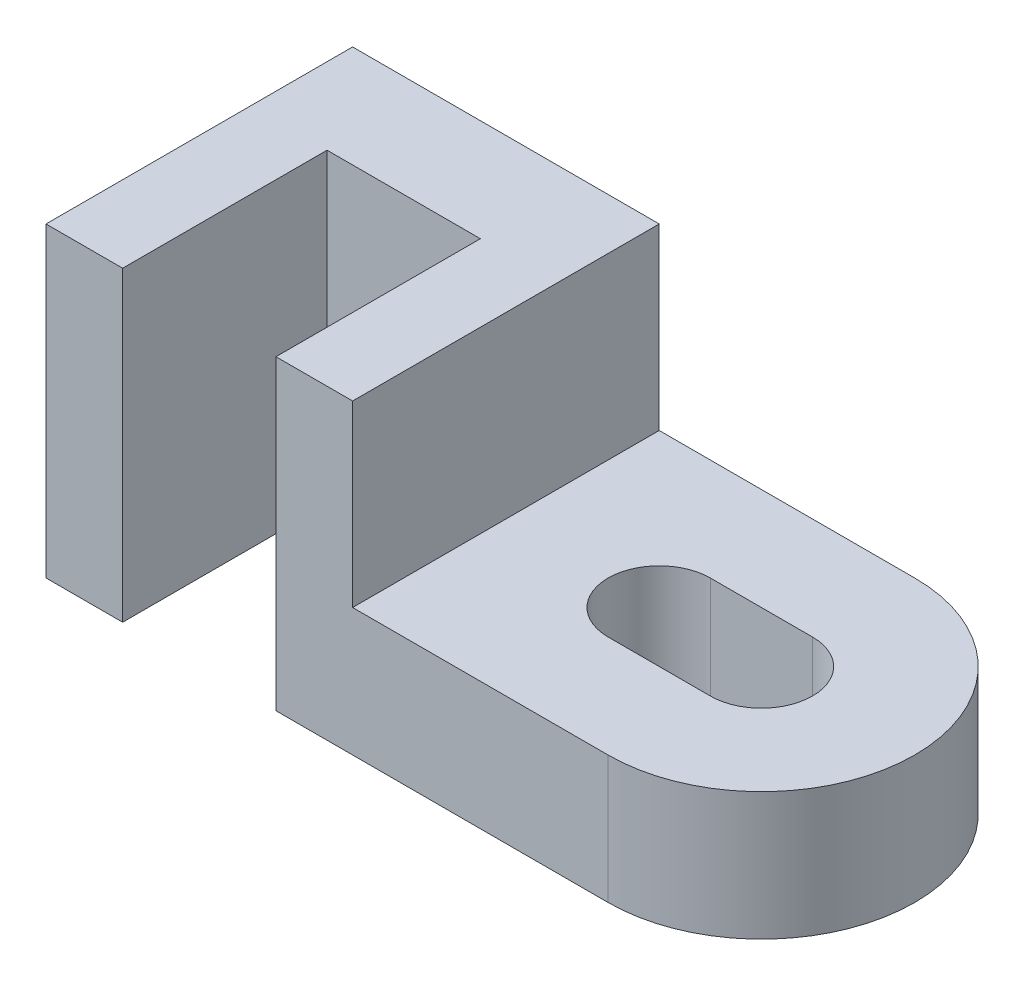
SolidWorks part; units mm, degrees
ref_plane "Front Plane" through (0, 0, 0) normal (0, 0, 1) x (1, 0, 0)
ref_plane "Top Plane" through (0, 0, 0) normal (0, 1, 0) x (1, 0, 0)
ref_plane "Right Plane" through (0, 0, 0) normal (1, 0, 0) x (0, 0, -1)
sketch "Sketch1" plane through (0, 0, 0) normal (0, 1, 0) x (1, 0, 0)
  line L0 (-29.3565, 0) -> (29.3565, 0) construction
  line L1 (0, -28.8348) -> (0, 28.8348) construction
  line L2 (0, 12) -> (0, -12)
  line L3 (0, -12) -> (-6, -12)
  line L4 (-6, -12) -> (-6, 4)
  line L5 (-6, 4) -> (-18, 4)
  line L6 (-18, 4) -> (-18, -12)
  line L7 (-18, -12) -> (-24, -12)
  line L8 (-24, -12) -> (-24, 12)
  line L9 (-24, 12) -> (0, 12)
  line L10 (0, 12) -> (20, 12)
  line L11 (20, -12) -> (0, -12)
  line L12 (20, 0) -> (12, 0) construction
  line L13 (20, -4) -> (12, -4)
  line L14 (20, 4) -> (12, 4)
  arc A0 (20, 12) -> (20, -12) centre (20, 0) cw
  arc A1 (20, -4) -> (20, 4) centre (20, 0) ccw
  arc A2 (12, 4) -> (12, -4) centre (12, 0) ccw
  point P3 (0, 0)
  point P4 (0, 0)
  point P8 (0, 0)
  point P21 (16, 0)
  point P26 (32, 0)
  point P27 (0, 0)
  point P28 (0, 0)
  dimension "D1" = 8
  dimension "D2" = 8
  dimension "D3" = 16
  dimension "D4" = 6
  dimension "D5" = 24
  dimension "D6" = 12
  dimension "D7" = 24
  dimension "D8" = 56
extrude "Boss-Extrude1" add sketch "Sketch1" along normal blind 24 contours L9 L8 L7 L6 L5 L4 L3 L2 region at (-0.3394, 0, 0)
extrude "Boss-Extrude2" add sketch "Sketch1<3>" along normal blind 10 contours A0 L10 L2 L11 A2 L14 A1 L13 region at (10, 0, -11.6)
sketch "Sketch1<3>" plane through (0, 0, 0) normal (0, 1, 0) x (1, 0, 0) same geometry as "Sketch1"
